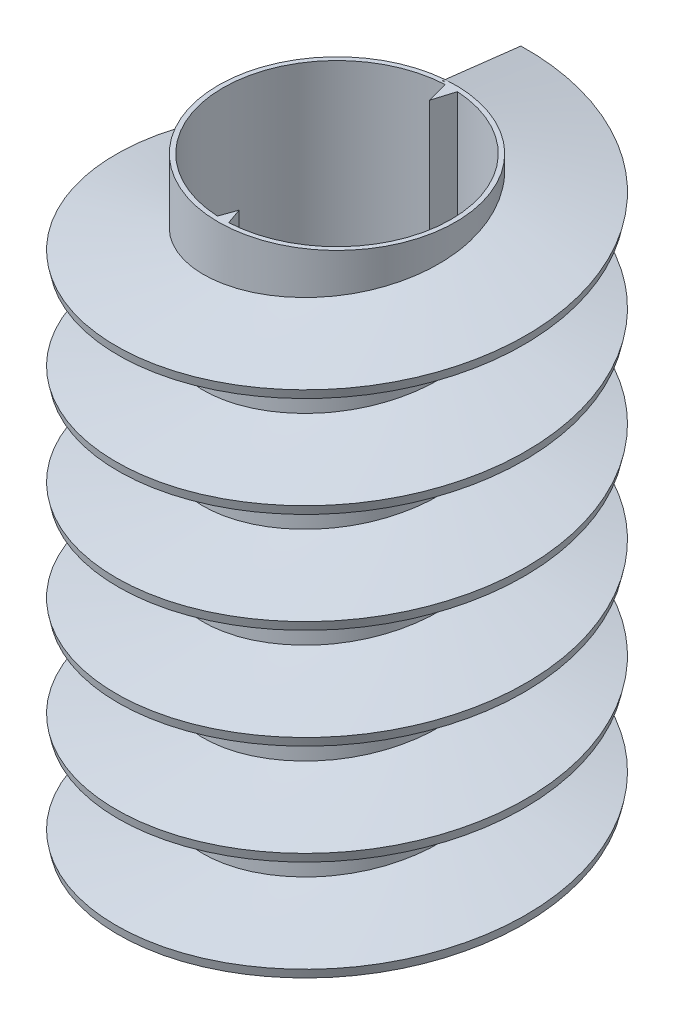
SolidWorks part; units mm, degrees
ref_plane "Front Plane" through (0, 0, 0) normal (0, 0, 1) x (1, 0, 0)
ref_plane "Top Plane" through (0, 0, 0) normal (0, 1, 0) x (1, 0, 0)
ref_plane "Right Plane" through (0, 0, 0) normal (1, 0, 0) x (0, 0, -1)
sketch "Sketch1" plane through (0, 0, 0) normal (0, 1, 0) x (1, 0, 0)
  circle A0 centre (0, 0) radius 2.6
  dimension "D1" = 5.2
extrude "Boss-Extrude1" add sketch "Sketch1" along normal blind 13
sketch "Sketch2" plane through (0, 13, 0) normal (0, 1, 0) x (1, 0, 0)
  line L0 (0.0734, 2.4989) -> (0.0755, 2.4989)
  line L1 (0.0755, 2.4989) -> (-0.1241, 2.4969)
  line L2 (0, 0) -> (0, 50000) construction
  line L3 (-0.1241, 2.4969) -> (0, 2.0268)
  line L4 (0, 2.0268) -> (0.1427, 2.4959)
  line L5 (0.1427, 2.4959) -> (-0.1241, 2.4969)
  line L6 (-0.1241, -2.4969) -> (0.1241, -2.4969)
  line L7 (0.1241, -2.4969) -> (0, -2.1457)
  line L8 (0, -2.1457) -> (-0.1241, -2.4969)
  circle A0 centre (0, 0) radius 2.5
extrude "Cut-Extrude1" cut sketch "Sketch2" against normal through all contours L2 L7 A0 L4 | L8 L2 L3 A0
ref_plane "Plane1" through (0, 13, 0) normal (0, 1, 0) x (1, 0, 0)
sketch "Sketch4" plane through (0, 13, 0) normal (0, 1, 0) x (1, 0, 0)
  circle A0 centre (0, 0) radius 2.6 construction
  circle A1 centre (0, 0) radius 2.6
curve "Helix/Spiral1" pitch 2.2 height 13.2 turns 6
ref_plane "Plane2" through (0, 0, 10) normal (0, 0, 1) x (1, 0, 0)
ref_plane "Plane3" through (-0.2266, -0.2, -2.5901) normal (0.9873, -0.1335, -0.0864) x (-0.1138, -0.2139, -0.9702)
sketch "Sketch8" plane through (-0.2266, -0.2, -2.5901) normal (0.9873, -0.1335, -0.0864) x (-0.1138, -0.2139, -0.9702)
  line L1 (-0.0508, -0.0049) -> (1.9492, -0.0049)
  line L2 (-0.0508, -0.0049) -> (-0.0508, -0.2049)
  line L3 (-0.0508, -0.2049) -> (1.9492, -0.2049)
  line L4 (1.9492, -0.0049) -> (1.9492, -0.2049)
  dimension "D1" = 0.2
  dimension "D2" = 2
sweep "Sweep1" add profiles "Sketch8" path "Helix/Spiral1"
